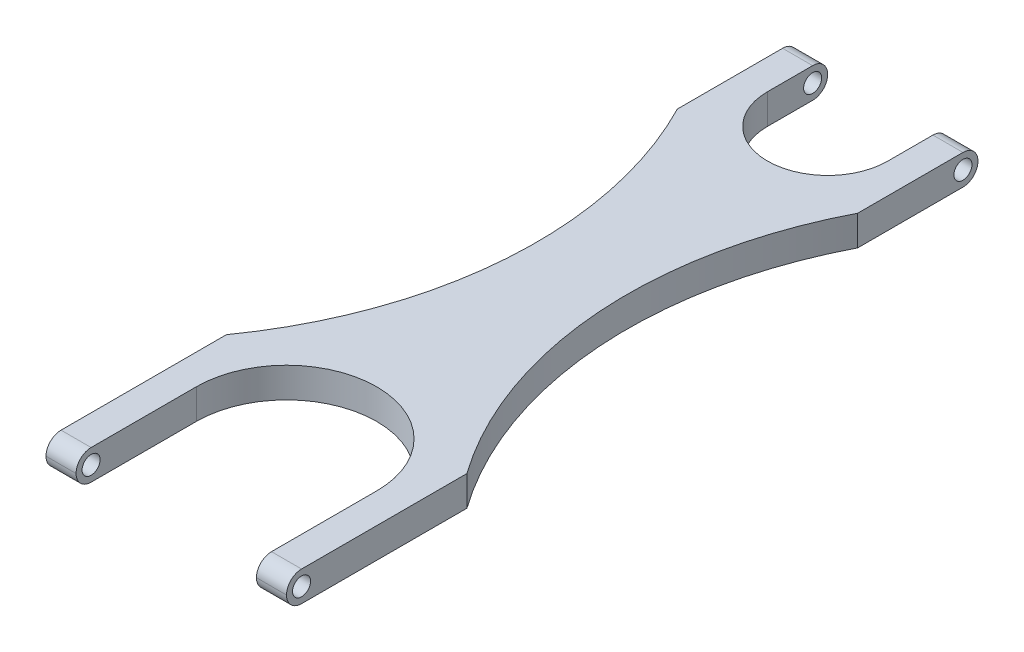
SolidWorks part; units mm, degrees
ref_plane "Front Plane" through (0, 0, 0) normal (0, 0, 1) x (1, 0, 0)
ref_plane "Top Plane" through (0, 0, 0) normal (0, 1, 0) x (1, 0, 0)
ref_plane "Right Plane" through (0, 0, 0) normal (1, 0, 0) x (0, 0, -1)
sketch "Sketch1" plane through (0, 0, 0) normal (0, 1, 0) x (1, 0, 0)
  line L0 (0, 0) -> (12.7, 0)
  line L1 (12.7, 0) -> (12.7, -25.4)
  line L2 (0, 0) -> (0, -50.8)
  line L3 (-12.7, -228.6) -> (-12.7, -304.8)
  line L4 (-12.7, -304.8) -> (0, -304.8)
  line L5 (0, -304.8) -> (0, -254)
  line L6 (38.1, -50.8) -> (38.1, -215.9) construction
  line L7 (76.2, -304.8) -> (76.2, -254)
  line L8 (88.9, -304.8) -> (76.2, -304.8)
  line L9 (88.9, -228.6) -> (88.9, -304.8)
  line L10 (76.2, 0) -> (76.2, -50.8)
  line L11 (63.5, 0) -> (63.5, -25.4)
  line L12 (76.2, 0) -> (63.5, 0)
  arc A0 (12.7, -25.4) -> (38.1, -50.8) centre (38.1, -25.4) ccw
  arc A1 (0, -50.8) -> (-12.7, -228.6) centre (-152.4, -129.2679) cw
  arc A2 (0, -254) -> (38.1, -215.9) centre (38.1, -254) cw
  arc A3 (76.2, -254) -> (38.1, -215.9) centre (38.1, -254) ccw
  arc A4 (63.5, -25.4) -> (38.1, -50.8) centre (38.1, -25.4) cw
  arc A5 (76.2, -50.8) -> (88.9, -228.6) centre (228.6, -129.2679) ccw
  dimension "D8" = 381
  dimension "D1" = 304.8
  dimension "D2" = 12.7
  dimension "D3" = 12.7
  dimension "D4" = 25.4
  dimension "D5" = 50.8
  dimension "D6" = 50.8
  dimension "D7" = 76.2
  dimension "D9" = 76.2
  dimension "D10" = 101.6
extrude "Boss-Extrude1" add sketch "Sketch1" along normal blind 12.7
fillet "Fillet1" radius 6.35 8 edges at (69.85, 0, 0) (6.35, 0, 0) (69.85, 12.7, 0) (6.35, 12.7, 0) (-6.35, 0, 304.8) (-6.35, 12.7, 304.8) (82.55, 0, 304.8) (82.55, 12.7, 304.8)
sketch "Sketch2" plane through (88.9, 0, 0) normal (1, 0, 0) x (0, 0, -1)
  circle A0 centre (-298.45, 6.35) radius 3.81
extrude "Cut-Extrude1" cut sketch "Sketch2" against normal through all
sketch "Sketch3" plane through (76.2, 0, 0) normal (1, 0, 0) x (0, 0, -1)
  circle A0 centre (-6.35, 6.35) radius 3.81
extrude "Cut-Extrude2" cut sketch "Sketch3" against normal through all
